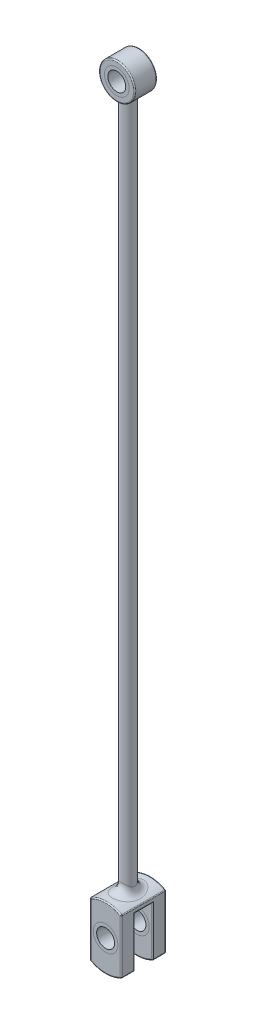
SolidWorks part; units mm, degrees
ref_plane "Front Plane" through (0, 0, 0) normal (0, 0, 1) x (1, 0, 0)
ref_plane "Top Plane" through (0, 0, 0) normal (0, 1, 0) x (1, 0, 0)
ref_plane "Right Plane" through (0, 0, 0) normal (1, 0, 0) x (0, 0, -1)
sketch "Sketch1" plane through (0, 0, 0) normal (0, 1, 0) x (1, 0, 0)
  circle A0 centre (0, 0) radius 1.5
  dimension "D1" = 3
extrude "Boss-Extrude1" add sketch "Sketch1" along normal blind 77.5 and the other way blind 78
sketch "Sketch2" plane through (0, 0, 0) normal (0, 0, 1) x (1, 0, 0)
  circle A0 centre (0, 80.5) radius 4
  circle A2 centre (0, 80.5) radius 2.75
  dimension "D1" = 8
  dimension "D2" = 80.5
  dimension "D5" = 5.5
extrude "Boss-Extrude2" add sketch "Sketch2" along normal mid plane 5
sketch "Sketch3" plane through (0, 0, 0) normal (0, 0, 1) x (1, 0, 0)
  circle A0 centre (0, 80.5) radius 2.75
  circle A1 centre (0, 80.5) radius 2
  dimension "D3" = 5.5
  dimension "D4" = 4
extrude "Boss-Extrude3" add sketch "Sketch3" along normal mid plane 5 separate body
sketch "Sketch4" plane through (0, 0, 0) normal (0, 0, 1) x (1, 0, 0)
  line L0 (3.5, -77.9378) -> (3.5, -90.0622)
  line L1 (-3.5, -77.9378) -> (-3.5, -90.0622)
  arc A0 (3.5, -77.9378) -> (-3.5, -77.9378) centre (0, -84) ccw
  arc A1 (-3.5, -90.0622) -> (3.5, -90.0622) centre (0, -84) ccw
  circle A2 centre (0, -84) radius 2.75
  dimension "D2" = 14
  dimension "D4" = 5.5
  dimension "D1" = 84
  dimension "D3" = 3.5
extrude "Boss-Extrude4" add sketch "Sketch4" along normal mid plane 10
sketch "Sketch6" plane through (0, 0, 0) normal (0, 0, 1) x (1, 0, 0)
  circle A0 centre (0, -84) radius 2.75
  circle A1 centre (0, -84) radius 2
  dimension "D1" = 5.5
  dimension "D2" = 4
extrude "Boss-Extrude6" add sketch "Sketch6" along normal mid plane 10 separate body
sketch "Sketch5" plane through (-3.5, 0, 0) normal (-1, 0, 0) x (0, 0, 1)
  line L0 (-2, -79) -> (2, -79)
  line L1 (2, -79) -> (2, -92.2501)
  line L2 (2, -92.2501) -> (-2, -92.2501)
  line L3 (-2, -92.2501) -> (-2, -79)
  point P2 (0, -79)
  dimension "D1" = 12
  dimension "D2" = 4
extrude "Cut-Extrude1" cut sketch "Sketch5" against normal through all
fillet "Fillet2" radius 2 1 edges at (-0.3068, -77.0067, -1.4683)
fillet "Fillet3" radius 0.5 1 edges at (0.2322, 76.5067, -1.4819)
fillet "Fillet4" radius 0.25 25 edges at (0, -91, -5) (0, -91, -2) (-3.5, -84, -5) (-3.5, -84, 5) (-3.5, -84.5311, 2) (-3.5, -79, 0) (-3.5, -84.5311, -2) (-3.5, -90.0622, -3.5) (3.5, -84.5311, 2) (3.5, -84, 5) (3.5, -84, -5) (3.5, -90.0622, -3.5) (3.5, -84.5311, -2) (3.5, -79, 0) (3.5, -77.9378, 0) (0, -77, 5) (-3.5, -77.9378, 0) (0, -77, -5) (0, -91, 5) (3.5, -90.0622, 3.5) (0, -91, 2) (-3.5, -90.0622, 3.5) (2.75, 80.5, -2.5) (4, 80.5, -2.5) (4, 80.5, 2.5)
